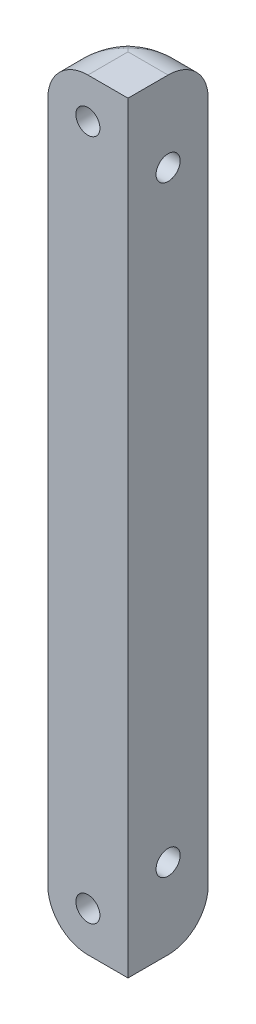
SolidWorks part; units mm, degrees
ref_plane "Front Plane" through (0, 0, 0) normal (0, 0, 1) x (1, 0, 0)
ref_plane "Top Plane" through (0, 0, 0) normal (0, 1, 0) x (1, 0, 0)
ref_plane "Right Plane" through (0, 0, 0) normal (1, 0, 0) x (0, 0, -1)
sketch "Sketch1" plane through (0, 0, 0) normal (0, 1, 0) x (1, 0, 0)
  line L1 (-6.35, -6.35) -> (6.35, -6.35)
  line L2 (-6.35, -6.35) -> (-6.35, 6.35)
  line L3 (-6.35, 6.35) -> (6.35, 6.35)
  line L4 (6.35, -6.35) -> (6.35, 6.35)
  line L5 (-6.35, -6.35) -> (6.35, 6.35) construction
  line L6 (-6.35, 6.35) -> (6.35, -6.35) construction
  point P0 (0, 0)
  dimension "D1" = 12.7
  dimension "D2" = 12.7
extrude "Boss-Extrude1" add sketch "Sketch1" along normal blind 120.65
sketch "Sketch2" plane through (0, 0, 6.35) normal (0, 0, 1) x (1, 0, 0)
  line L0 (-6.35, 0) -> (6.35, 0) construction
  line L1 (-6.35, 120.65) -> (6.35, 120.65) construction
  circle A0 centre (0, 6.35) radius 1.905
  circle A1 centre (0, 114.3) radius 1.905
  dimension "D1" = 3.81
  dimension "D2" = 6.35
  dimension "D3" = 6.35
extrude "Cut-Extrude1" cut sketch "Sketch2" against normal through all
sketch "Sketch3" plane through (6.35, 0, 0) normal (1, 0, 0) x (0, 0, -1)
  line L0 (-6.35, 0) -> (6.35, 0) construction
  line L1 (-6.35, 120.65) -> (6.35, 120.65) construction
  circle A0 centre (0, 107.95) radius 1.905
  circle A1 centre (0, 12.7) radius 1.905
  dimension "D3" = 3.81
  dimension "D1" = 12.7
  dimension "D2" = 12.7
extrude "Cut-Extrude2" cut sketch "Sketch3" against normal through all
chamfer "Chamfer1" distance 9.525 angle 45 1 edges at (-6.35, 60.325, -6.35)
fillet "Fillet1" radius 6.35 4 edges at (4.7625, 0, -6.35) (-6.35, 0, 4.7625) (4.7625, 120.65, -6.35) (-6.35, 120.65, 4.7625)
fillet "Fillet2" radius 1.5875 6 edges at (-5.0201, 118.1886, 1.8451) (-5.0201, 2.4614, 1.8451) (-6.35, 60.325, 3.175) (1.8451, 2.4614, -5.0201) (1.8451, 118.1886, -5.0201) (3.175, 60.325, -6.35)
